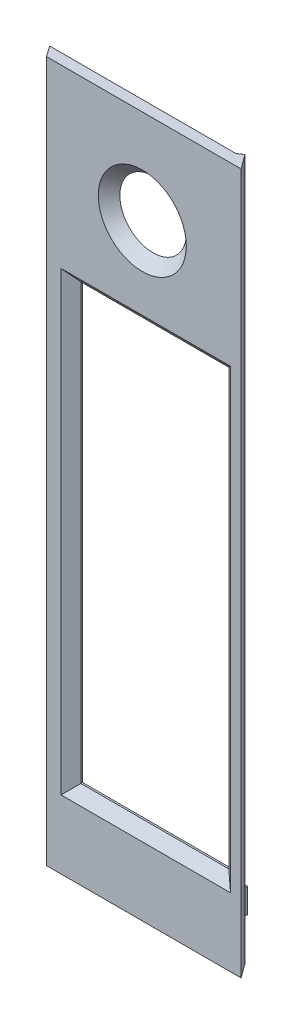
SolidWorks part; units mm, degrees
ref_plane "前视基准面" through (0, 0, 0) normal (0, 0, 1) x (1, 0, 0)
ref_plane "上视基准面" through (0, 0, 0) normal (0, 1, 0) x (1, 0, 0)
ref_plane "右视基准面" through (0, 0, 0) normal (1, 0, 0) x (0, 0, -1)
other "Configuration Table"
sketch "草图1" plane through (0, 0, 0) normal (0, 0, 1) x (1, 0, 0)
  line L2 (-39.759, 32.5) -> (-22.481, 32.5)
  line L3 (-39.759, 32.5) -> (-39.759, -32.5)
  line L4 (-39.759, -32.5) -> (-22.481, -32.5)
  line L5 (-22.481, 32.5) -> (-22.481, -32.5)
  line L6 (-36.7043, 15.1564) -> (-22.9829, 15.1564)
  line L7 (-36.7043, 15.1564) -> (-36.7043, -25.1449)
  line L8 (-36.7043, -25.1449) -> (-22.9829, -25.1449)
  line L9 (-22.9829, 15.1564) -> (-22.9829, -25.1449)
  circle A0 centre (-30.1677, 23.76) radius 3.082
extrude "凸台-拉伸1" add sketch "草图1" along normal blind 1
sketch "草图2" plane through (0, 0, 0) normal (0, 0, -1) x (-1, 0, 0)
  line L0 (36.2677, 24.6976) -> (36.2677, 27.7216)
  line L1 (36.2677, -26.5) -> (36.2677, 28.06) construction
  line L2 (36.2677, 27.7216) -> (34.9293, 29.06)
  line L3 (35.2677, 29.06) -> (25.3677, 29.06) construction
  line L4 (34.9293, 29.06) -> (31.366, 29.06)
  line L5 (31.366, 29.06) -> (31.366, 28.3185)
  line L6 (31.366, 28.3185) -> (35.2677, 24.6976)
  line L7 (35.2677, 24.6976) -> (36.2677, 24.6976)
  line L8 (28.8258, 29.06) -> (26.3916, 29.06)
  line L9 (26.3916, 29.06) -> (24.3677, 27.036)
  line L10 (24.3677, 28.06) -> (24.3677, 18.46) construction
  line L11 (24.3677, 27.036) -> (24.3677, 24.9699)
  line L12 (24.3677, 24.9699) -> (25.4773, 24.9699)
  line L13 (25.4773, 24.9699) -> (28.8258, 28.3185)
  line L14 (28.8258, 28.3185) -> (28.8258, 29.06)
  line L16 (34.5713, -29.9151) -> (23.2046, -29.9151)
  line L17 (34.5713, -29.9151) -> (34.5713, -27.6352)
  line L18 (34.5713, -27.6352) -> (23.2046, -27.6352)
  line L19 (23.2046, -29.9151) -> (23.2046, -27.6352)
extrude "凸台-拉伸2" add sketch "草图2" along normal blind 1.8
sketch "草图3" plane through (0, -32.5, 0) normal (0, -1, 0) x (1, 0, 0)
  line L0 (-22.481, 1) -> (-20.9972, 1)
  line L1 (-20.9972, 1) -> (-21.7391, 0)
  line L2 (-21.7391, 0) -> (-22.481, 0)
  line L3 (-22.481, 0) -> (-22.481, 1)
extrude "凸台-拉伸3" add sketch "草图3" against normal up to surface (65 mm away) up to face at (-31.12, 32.5, 0.5)
sketch "草图4" plane through (0, -32.5, 0) normal (0, -1, 0) x (1, 0, 0)
  line L1 (-40.3821, -0.8899) -> (-38.6479, 1.5868) construction
  line L8 (-40.9576, -1.7118) -> (-39.759, 0) construction
  line L9 (-39.759, 0) -> (-39.0588, 1)
  line L10 (-39.759, 1) -> (-20.9972, 1) construction
  line L11 (-39.0588, 1) -> (-39.759, 1)
  line L12 (-39.759, 1) -> (-39.759, 0)
extrude "切除-拉伸1" cut sketch "草图4" against normal up to surface (65 mm away) up to face at (-30.5636, 32.5, 0.5)
sketch "草图5" plane through (0, -32.5, 0) normal (0, -1, 0) x (1, 0, 0)
  line L0 (-21.7391, 0) -> (-21.9832, -0.3486)
  line L1 (-21.2387, -0.8699) -> (-22.481, 0) construction
  line L2 (-21.9832, -0.3486) -> (-22.481, 0)
  line L3 (-39.759, 0) -> (-21.7391, 0) construction
  line L4 (-22.481, 0) -> (-21.7391, 0)
extrude "凸台-拉伸4" add sketch "草图5" against normal up to surface (65 mm away) up to face at (-30.3885, 32.5, 0.5)
chamfer "倒角1" distance 1 angle 45 1 edges at (-27.0856, 23.76, 1)
chamfer "倒角2" distance 1 angle 40 4 edges at (-29.8436, 15.1564, 1) (-36.7043, -4.9942, 1) (-22.9829, -4.9942, 1) (-29.8436, -25.1449, 1) first distance on face at (-26.0856, 23.76, 1)
